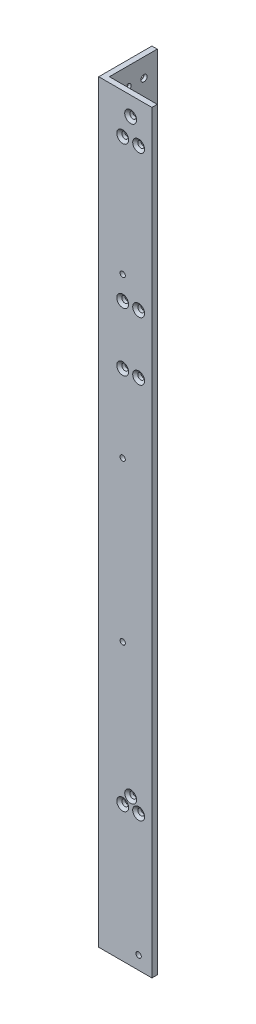
SolidWorks part; units mm, degrees
ref_plane "Front Plane" through (0, 0, 0) normal (0, 0, 1) x (1, 0, 0)
ref_plane "Top Plane" through (0, 0, 0) normal (0, 1, 0) x (1, 0, 0)
ref_plane "Right Plane" through (0, 0, 0) normal (1, 0, 0) x (0, 0, -1)
sketch "Sketch2" plane through (0, 0, 0) normal (0, 1, 0) x (1, 0, 0)
  line L0 (0, 31.75) -> (3.175, 31.75)
  line L1 (3.175, 31.75) -> (3.175, 3.175)
  line L2 (3.175, 3.175) -> (31.75, 3.175)
  line L3 (31.75, 3.175) -> (31.75, 0)
  line L4 (31.75, 0) -> (0, 0)
  line L5 (0, 0) -> (0, 31.75)
  point P9 (1.5875, 31.75)
  point P10 (31.75, 1.5875)
  dimension "D4" = 3.175
  dimension "D1" = 31.75
  dimension "D2" = 31.75
  dimension "D3" = 3.175
extrude "Boss-Extrude1" add sketch "Sketch2" along normal blind 450
sketch "RightSideHoles-Sketch3" plane through (0, 0, 0) normal (0, 0, 1) x (1, 0, 0)
  line L0 (0, 0) -> (31.75, 0) construction
  line L1 (0, 450) -> (31.75, 450) construction
  line L3 (0, 450) -> (0, 0) construction
  circle A0 centre (14.2875, 81.1125) radius 1.5875
  circle A1 centre (23.8125, 81.1125) radius 1.5875
  circle A3 centre (19.05, 87.4625) radius 1.5875
  circle A5 centre (14.2875, 426.1875) radius 1.5875
  circle A6 centre (19.05, 438.8875) radius 1.5875
  circle A7 centre (23.8125, 426.1875) radius 1.5875
  circle A8 centre (14.2875, 341.2474) radius 1.5875
  circle A9 centre (23.8125, 341.2474) radius 1.5875
  circle A10 centre (14.2875, 306.3224) radius 1.5875
  circle A11 centre (23.8125, 306.3224) radius 1.5875
  circle A13 centre (23.8125, 7.9375) radius 1.5875
  circle A14 centre (14.2875, 165) radius 1.5875
  circle A15 centre (14.2875, 260) radius 1.5875
  circle A16 centre (14.2875, 355) radius 1.5875
  dimension "D4" = 3.175
  dimension "D1" = 81.1125
  dimension "D2" = 14.2875
  dimension "D7" = 34.925
  dimension "D10" = 341.2474
  dimension "D11" = 165
  dimension "D13" = 95
  dimension "D5" = 6.35
  dimension "D6" = 12.7
  dimension "D8" = 11.1125
  dimension "D9" = 95
  dimension "D3" = 7.9375
  dimension "D12" = 23.8125
  dimension "D14" = 19.05
sketch "FrontSideHoles-Sketch4" plane through (0, 0, 0) normal (-1, 0, 0) x (0, 0, 1)
  line L0 (-31.75, 450) -> (0, 450) construction
  line L1 (0, 450) -> (0, 0) construction
  line L3 (-31.75, 0) -> (0, 0) construction
  circle A0 centre (-19.05, 81.1125) radius 1.5875
  circle A2 centre (-23.8125, 87.4625) radius 1.5875
  circle A3 centre (-14.2875, 87.4625) radius 1.5875
  circle A4 centre (-23.8125, 438.8875) radius 1.5875
  circle A5 centre (-14.2875, 438.8875) radius 1.5875
  circle A6 centre (-19.05, 426.1875) radius 1.5875
  circle A8 centre (-17.4625, 354.1849) radius 2
  circle A9 centre (-17.4625, 313.9849) radius 2
  circle A10 centre (-14.2875, 165) radius 1.5875
  circle A11 centre (-14.2875, 260) radius 1.5875
  circle A13 centre (-23.8125, 7.9375) radius 1.5875
  dimension "D4" = 3.175
  dimension "D13" = 95
  dimension "D5" = 6.35
  dimension "D16" = 4
  dimension "D6" = 11.1125
  dimension "D9" = 40.2
  dimension "D10" = 17.4625
  dimension "D7" = 12.7
  dimension "D12" = 165
  dimension "D15" = 7.9375
  dimension "D2" = 14.2875
  dimension "D3" = 81.1125
  dimension "D8" = 354.1849
  dimension "D14" = 19.05
  dimension "D11" = 23.8125
extrude "RightSideHoles-Cut-Extrude1" cut sketch "RightSideHoles-Sketch3" against normal blind 3.175
extrude "FrontSideHoles-Cut-Extrude2" cut sketch "FrontSideHoles-Sketch4" against normal blind 3.175
sketch "Sketch5" plane through (0, 0, 0) normal (-1, 0, 0) x (0, 0, 1)
  point P0 (-23.8125, 438.8875)
  point P3 (-19.05, 426.1875)
  point P6 (-14.2875, 438.8875)
  point P9 (-19.05, 81.1125)
  point P12 (-14.2875, 87.4625)
  point P15 (-23.8125, 87.4625)
hole_wizard "CSK for #6 Flat Head Machine Screw (100)2" positions "Sketch5" profile "Sketch6" countersink size "#6" standard "ANSI Inch" end condition through all
sketch "Sketch6" plane through (0, 438.8875, -23.8125) normal (0, 1, 0) x (0, 0, 1)
  line L0 (0, 0) -> (0, 31.75)
  line L1 (0, 31.75) -> (1.8986, 31.75)
  line L2 (1.8986, 31.75) -> (1.8986, 1.38)
  line L3 (1.8986, 1.38) -> (3.5433, 0)
  line L5 (3.5433, 0) -> (0, 0)
  line L6 (-1.8986, 1.38) -> (-3.5433, 0) construction
  line L11 (0, -6.35) -> (0, 107.95) construction
  dimension "Thru Hole Dia." = 3.7973
  dimension "Thru Hole Depth" = 31.75
  dimension "Near C'Sink Dia." = 7.0866
  dimension "Near C'Sink Angle" = 100
sketch "Sketch11" plane through (0, 0, 0) normal (0, 0, 1) x (1, 0, 0)
  point P0 (14.2875, 81.1125)
  point P3 (19.05, 87.4625)
  point P6 (23.8125, 81.1125)
  point P9 (14.2875, 306.3224)
  point P12 (23.8125, 306.3224)
  point P15 (14.2875, 341.2474)
  point P18 (23.8125, 341.2474)
  point P21 (14.2875, 426.1875)
  point P24 (23.8125, 426.1875)
  point P27 (19.05, 438.8875)
hole_wizard "CSK for #6 Flat Head Machine Screw (100)3" positions "Sketch11" profile "Sketch12" countersink size "#6" standard "ANSI Inch" end condition through all
sketch "Sketch12" plane through (14.2875, 81.1125, 0) normal (1, 0, 0) x (0, -1, 0)
  line L0 (0, 0) -> (0, 31.75)
  line L1 (0, 31.75) -> (1.8986, 31.75)
  line L2 (1.8986, 31.75) -> (1.8986, 1.38)
  line L3 (1.8986, 1.38) -> (3.5433, 0)
  line L5 (3.5433, 0) -> (0, 0)
  line L6 (-1.8986, 1.38) -> (-3.5433, 0) construction
  line L11 (0, -6.35) -> (0, 107.95) construction
  dimension "Thru Hole Dia." = 3.7973
  dimension "Thru Hole Depth" = 31.75
  dimension "Near C'Sink Dia." = 7.0866
  dimension "Near C'Sink Angle" = 100
equation "\"RailThickness\"= .125in'Spec"
equation "\"VSWidth\"= 1.25in'Spec"
equation "\"VSHeight\"= 1.25in'Spec"
equation "\"VSLength\"= 450mm"
equation "\"HoleOffsetFromEdge\"= \"RailThickness\" * 2.5"
equation "\"HoleOffsetFromSide\"= \"RailThickness\" * 3.5"
equation "\"LegHeight\"= 70mm'Space needed for PSU/Stepper/Electronics"
equation "\"VSBottomSideRailHoleY1FromBottomOfLowerRail\"= \"V1 BottomOfLowerRail\" + \"HoleOffsetFromSide\"'Equals 81.1125"
equation "\"VSSideRailHoleX1FromSide\"= \"HoleOffsetFromSide\" + \"RailThickness\""
equation "\"FasteningHoleDiameter\"= .125in"
equation "\"VSBottomSideRailHoleY2FromY1\"= \"LowerRailHeight\" - \"HoleOffsetFromSide\" - \"HoleOffsetFromEdge\"'Equals 6.35"
equation "\"VSTopSideRailHoleY1FromEdge\"= \"HoleOffsetFromEdge\" + \"RailThickness\""
equation "\"D4@RightSideHoles-Sketch3\" = \"FasteningHoleDiameter\""
equation "\"D1@RightSideHoles-Sketch3\" = \"VSBottomSideRailHoleY1FromBottomOfLowerRail\""
equation "\"D2@RightSideHoles-Sketch3\" = \"VSSideRailHoleX1FromSide\""
equation "\"D1@Boss-Extrude1\"=\"VSLength\""
equation "\"D4@FrontSideHoles-Sketch4\" = \"FasteningHoleDiameter\""
equation "\"D6@FrontSideHoles-Sketch4\" = \"VSTopSideRailHoleY1FromEdge\""
equation "\"VSMidSideRailHoleY1FromV8TopOfMidSideRail\"= \"V8 ToTopOfMidSideRail\" - \"HoleOffsetFromEdge\"'Equals 341.24737"
equation "\"LowerRailHeight\"= 1.00in"
equation "\"D2@Sketch2\"=\"VSWidth\""
equation "\"D1@Sketch2\"=\"VSHeight\""
equation "\"TopRailHeight\"= 1.25in"
equation "\"MidLeftOrRightSideRailHeight\"= 2.0in"
equation "\"VSMidSideRailHoleY2FromY1\"= \"MidLeftOrRightSideRailHeight\" - \"HoleOffsetFromEdge\" * 2'Equals 34.925"
equation "\"D7@RightSideHoles-Sketch3\"=\"VSMidSideRailHoleY2FromY1\""
equation "\"VSTopSideRailHoleY2FromY1\"= \"TopRailHeight\" - \"VSTopSideRailHoleY1FromEdge\" - \"HoleOffsetFromEdge\"'Equals 12.7"
equation "\"D7@FrontSideHoles-Sketch4\"=\"VSTopSideRailHoleY2FromY1\""
equation "\"VSSideRailHoleX2FromSide\"= \"VSWidth\" - \"HoleOffsetFromEdge\""
equation "\"1mmSpacer\"= 1mm"
equation "\"20TGT2PulleyWidth\"= 8.7mm'The STL of the Pulley in the diagram is a bit larger"
equation "\"BeltTensionerInnerHeight\"= \"20TGT2PulleyWidth\" * 2 + \"1mmSpacer\" * 3"
equation "\"BeltTensionerHeight\"= 60mm"
equation "\"D9@FrontSideHoles-Sketch4\"=\"VSBeltTensionerHoleY2FromY1\""
equation "\"VSBeltTensionerHoleY1ToAlignedWithYAxisGantryBlockUpperPulley\"= \"V5 ToBottomOfXAxisLinearRail\" - \"DistanceFromXAxisLinearRailBottomAndTopGantryPulley\" + \"DistanceFromBeltTensionerTopPulleyToBeltTensionerTop\" - \"BeltTensionerMountingHoleOffsetFromTopOrBottom\"'Equals 354.18487"
equation "\"VSBeltTensionerHoleY2FromY1\"= \"BeltTensionerHeight\" - \"BeltTensionerMountingHoleOffsetFromTopOrBottom\" * 2"
equation "\"V1 BottomOfLowerRail\"= \"LegHeight\""
equation "\"StepperShaftLength\"= 24mm'Pulley will be attached to the end"
equation "\"ZAxisLeadScrewLength\"= 200mm"
equation "\"LM8UUHeight\"= 24mm'Spec"
equation "\"V2 ToBedAtTopOfZAxis\"= \"V1 BottomOfLowerRail\" - \"LowerEnclosureThickness\" + \"StepperShaftLength\" + \"ZAxisLeadScrewLength\" - \"LM8UUHeight\" / 2'Equals 277"
equation "\"HotEndToTopOfXAxisGB\"= 71.68487mm'Equals 71.68487. Measured after installed onto X-Axis linear rail guide block"
equation "\"TopOfGBToBottomOfLinearRail\"= \"LinearGBWidth\" / 2 + \"LinearRailWidth\" / 2'Equals 19.5"
equation "\"LinearGBWidth\"= 27mm'Spec"
equation "\"V5 ToBottomOfXAxisLinearRail\"= \"V4 ToTopOfBuildPlate/HotEndTip\" + \"HotEndToTopOfXAxisGB\" - \"TopOfGBToBottomOfLinearRail\"'Equals 352.18487"
equation "\"LinearRailWidth\"= 12mm'Spec"
equation "\"V6 ToMiddleOfYAxisGantryBlock\"= \"V5 ToBottomOfXAxisLinearRail\" - \"GABHeight\" / 2'Equals 334.18487"
equation "\"GABUpperHeight\"= 4mm"
equation "\"GABMidWallHeight\"= 28mm'Must equal 28 or changes alignment"
equation "\"D10@RightSideHoles-Sketch3\"=\"VSMidSideRailHoleY1FromV8TopOfMidSideRail\""
equation "\"BedToBuildPlateStandoffLength\"= 15mm"
equation "\"BuildPlateHeight\"= 8mm'Spec"
equation "\"V4 ToTopOfBuildPlate/HotEndTip\"= \"V2 ToBedAtTopOfZAxis\" + \"BedToBuildPlateStandoffLength\" + \"BuildPlateHeight\""
equation "\"V8 ToTopOfMidSideRail\"= \"V6 ToMiddleOfYAxisGantryBlock\" + \"MidSideRailVerticalOffset\"'Equals 349.18487"
equation "\"BeltTensionerMountingHoleOffsetFromEdge\"= \"HoleOffsetFromEdge\" + \"RailThickness\" * 2"
equation "\"VSBeltTensionerXMountingHoleOffsetFromSide\"= \"BeltTensionerMountingHoleOffsetFromEdge\" + \"RailThickness\""
equation "\"D10@FrontSideHoles-Sketch4\"=\"VSBeltTensionerXMountingHoleOffsetFromSide\""
equation "\"VSEnclosureOffsets\"= ( \"VSLength\" - \"LegHeight\" ) / 4"
equation "\"D11@RightSideHoles-Sketch3\"=\"LegHeight\" + \"VSEnclosureOffsets\""
equation "\"D13@RightSideHoles-Sketch3\"=\"VSEnclosureOffsets\""
equation "\"D12@FrontSideHoles-Sketch4\"= \"LegHeight\" + \"VSEnclosureOffsets\""
equation "\"D13@FrontSideHoles-Sketch4\"=\"VSEnclosureOffsets\""
equation "\"D15@FrontSideHoles-Sketch4\"=\"HoleOffsetFromEdge\""
equation "\"D2@FrontSideHoles-Sketch4\"=\"VSSideRailHoleX1FromSide\""
equation "\"D5@FrontSideHoles-Sketch4\"=\"VSBottomSideRailHoleY2FromY1\""
equation "\"D3@FrontSideHoles-Sketch4\"=\"VSBottomSideRailHoleY1FromBottomOfLowerRail\""
equation "\"D5@RightSideHoles-Sketch3\"=\"VSBottomSideRailHoleY2FromY1\""
equation "\"D6@RightSideHoles-Sketch3\"=\"VSTopSideRailHoleY2FromY1\""
equation "\"D8@RightSideHoles-Sketch3\"=\"VSTopSideRailHoleY1FromEdge\""
equation "\"BeltTensionerMountingHoleDiameter\"= 4.0mm"
equation "\"D16@FrontSideHoles-Sketch4\"=\"BeltTensionerMountingHoleDiameter\""
equation "\"LowerEnclosureThickness\"= 5mm"
equation "\"GABLowerHeight\"= 4mm"
equation "\"GABHeight\"= \"GABLowerHeight\" + \"GABMidWallHeight\" + \"GABUpperHeight\""
equation "\"D9@RightSideHoles-Sketch3\"=\"VSEnclosureOffsets\""
equation "\"BeltTensionerMountingHoleOffsetFromTopOrBottom\"= ( \"BeltTensionerHeight\" - \"BeltTensionerInnerHeight\" ) / 4"
equation "\"MidSideRailVerticalOffset\"= \"LinearRailWidth\" + 3mm'Allows space for RodStabilizer to attach to bottom of MidSideRail"
equation "\"GABRiserBossOffset\"= 0.4mm'Aligns Pulleys inside edges to be 2.5mm (.5mm apart top to bottom)"
equation "\"GABMidShortRiserHeight\"= \"GABMidWallHeight\" / 2 - \"20TGT2PulleyWidth\"'Equals 5.3"
equation "\"7mmx1mmSpacerHeight\"= 1mm"
equation "\"D8@FrontSideHoles-Sketch4\"=\"VSBeltTensionerHoleY1ToAlignedWithYAxisGantryBlockUpperPulley\""
equation "\"DistanceFromXAxisLinearRailBottomAndTopGantryPulley\"= \"GABUpperHeight\" + \"GABMidShortRiserHeight\" - \"GABRiserBossOffset\"'Equals 8.9"
equation "\"DistanceFromBeltTensionerTopPulleyToBeltTensionerTop\"= \"7mmx1mmSpacerHeight\" + \"BeltTensionerTopHeight\"'Equals 20.8"
equation "\"BeltTensionerTopHeight\"= ( \"BeltTensionerHeight\" - \"BeltTensionerInnerHeight\" ) / 2'Equals 19.8"
equation "\"VSMidSideRailHoleXFromSideToCenter\"= \"RailThickness\" * 6"
equation "\"D14@FrontSideHoles-Sketch4\"=\"VSMidSideRailHoleXFromSideToCenter\""
equation "\"D3@RightSideHoles-Sketch3\"=\"HoleOffsetFromEdge\""
equation "\"D14@RightSideHoles-Sketch3\"=\"VSMidSideRailHoleXFromSideToCenter\""
equation "\"D12@RightSideHoles-Sketch3\"=\"VSSideRailHoleX2FromSide\""
equation "\"D11@FrontSideHoles-Sketch4\"=\"VSSideRailHoleX2FromSide\""
